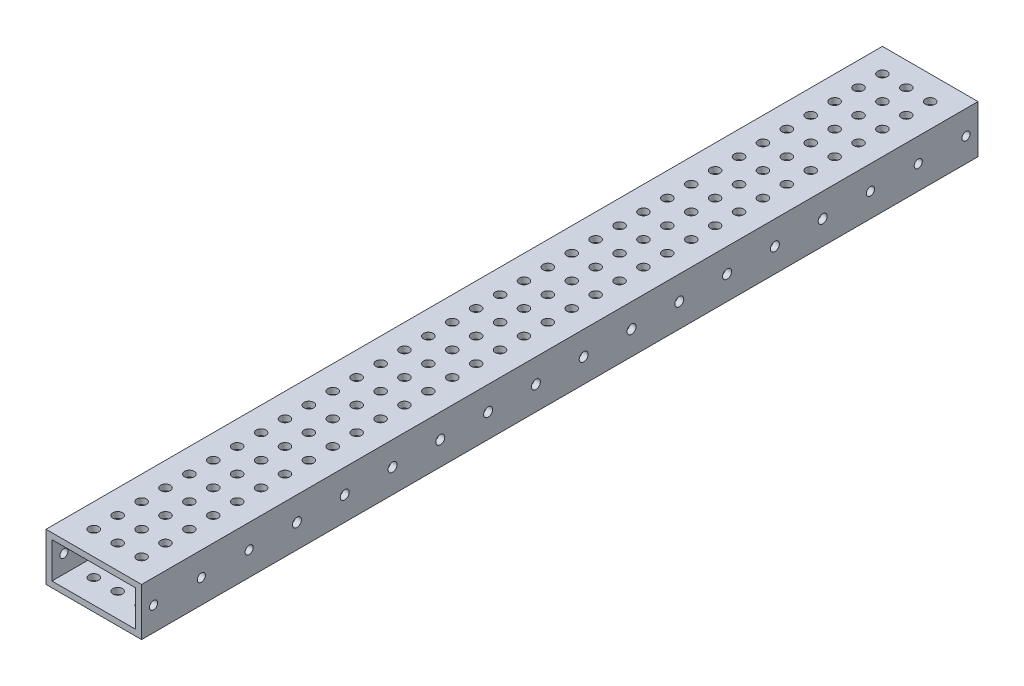
SolidWorks part; units mm, degrees
ref_plane "Front Plane" through (0, 0, 0) normal (0, 0, 1) x (1, 0, 0)
ref_plane "Top Plane" through (0, 0, 0) normal (0, 1, 0) x (1, 0, 0)
ref_plane "Right Plane" through (0, 0, 0) normal (1, 0, 0) x (0, 0, -1)
sketch "Sketch1" plane through (0, 0, 0) normal (0, 0, 1) x (1, 0, 0)
  line L0 (-22.225, 9.525) -> (22.225, 9.525)
  line L1 (-25.4, 12.7) -> (25.4, 12.7)
  line L2 (-25.4, 12.7) -> (-25.4, -12.7)
  line L3 (-25.4, -12.7) -> (25.4, -12.7)
  line L4 (25.4, 12.7) -> (25.4, -12.7)
  line L5 (22.225, 9.525) -> (22.225, -9.525)
  line L6 (-22.225, -9.525) -> (22.225, -9.525)
  line L7 (-22.225, 9.525) -> (-22.225, -9.525)
  line L8 (-25.4, 12.7) -> (25.4, -12.7) construction
  line L9 (25.4, 12.7) -> (-25.4, -12.7) construction
  point P5 (0, 0)
  dimension "D1" = 50.8
  dimension "D2" = 25.4
  dimension "D3" = 3.175
extrude "Boss-Extrude1" add sketch "Sketch1" along normal mid plane 444.5
sketch "Sketch2" plane through (0, 12.7, 0) normal (0, 1, 0) x (1, 0, 0)
  line L0 (25.4, -222.25) -> (-25.4, -222.25) construction
  line L1 (-25.4, -222.25) -> (-25.4, 222.25) construction
  line L2 (-12.7, -209.55) -> (0, -209.55) construction
  line L3 (0, -209.55) -> (12.7, -209.55) construction
  line L4 (25.4, 222.25) -> (-25.4, 222.25) construction
  circle A0 centre (0, -209.55) radius 2.5527
  circle A1 centre (12.7, -209.55) radius 2.5527
  circle A2 centre (-12.7, -209.55) radius 2.5527
  circle A3 centre (-12.7, -196.85) radius 2.5527
  circle A4 centre (0, -196.85) radius 2.5527
  circle A5 centre (12.7, -196.85) radius 2.5527
  circle A6 centre (-12.7, -184.15) radius 2.5527
  circle A7 centre (0, -184.15) radius 2.5527
  circle A8 centre (12.7, -184.15) radius 2.5527
  circle A9 centre (-12.7, -171.45) radius 2.5527
  circle A10 centre (0, -171.45) radius 2.5527
  circle A11 centre (12.7, -171.45) radius 2.5527
  circle A12 centre (-12.7, -158.75) radius 2.5527
  circle A13 centre (0, -158.75) radius 2.5527
  circle A14 centre (12.7, -158.75) radius 2.5527
  circle A15 centre (-12.7, -146.05) radius 2.5527
  circle A16 centre (0, -146.05) radius 2.5527
  circle A17 centre (12.7, -146.05) radius 2.5527
  circle A18 centre (-12.7, -133.35) radius 2.5527
  circle A19 centre (0, -133.35) radius 2.5527
  circle A20 centre (12.7, -133.35) radius 2.5527
  circle A21 centre (-12.7, -120.65) radius 2.5527
  circle A22 centre (0, -120.65) radius 2.5527
  circle A23 centre (12.7, -120.65) radius 2.5527
  circle A24 centre (-12.7, -107.95) radius 2.5527
  circle A25 centre (0, -107.95) radius 2.5527
  circle A26 centre (12.7, -107.95) radius 2.5527
  circle A27 centre (-12.7, -95.25) radius 2.5527
  circle A28 centre (0, -95.25) radius 2.5527
  circle A29 centre (12.7, -95.25) radius 2.5527
  circle A30 centre (-12.7, -82.55) radius 2.5527
  circle A31 centre (0, -82.55) radius 2.5527
  circle A32 centre (12.7, -82.55) radius 2.5527
  circle A33 centre (-12.7, -69.85) radius 2.5527
  circle A34 centre (0, -69.85) radius 2.5527
  circle A35 centre (12.7, -69.85) radius 2.5527
  circle A36 centre (-12.7, -57.15) radius 2.5527
  circle A37 centre (0, -57.15) radius 2.5527
  circle A38 centre (12.7, -57.15) radius 2.5527
  circle A39 centre (-12.7, -44.45) radius 2.5527
  circle A40 centre (0, -44.45) radius 2.5527
  circle A41 centre (12.7, -44.45) radius 2.5527
  circle A42 centre (-12.7, -31.75) radius 2.5527
  circle A43 centre (0, -31.75) radius 2.5527
  circle A44 centre (12.7, -31.75) radius 2.5527
  circle A45 centre (-12.7, -19.05) radius 2.5527
  circle A46 centre (0, -19.05) radius 2.5527
  circle A47 centre (12.7, -19.05) radius 2.5527
  circle A48 centre (-12.7, -6.35) radius 2.5527
  circle A49 centre (0, -6.35) radius 2.5527
  circle A50 centre (12.7, -6.35) radius 2.5527
  circle A51 centre (-12.7, 6.35) radius 2.5527
  circle A52 centre (0, 6.35) radius 2.5527
  circle A53 centre (12.7, 6.35) radius 2.5527
  circle A54 centre (-12.7, 19.05) radius 2.5527
  circle A55 centre (0, 19.05) radius 2.5527
  circle A56 centre (12.7, 19.05) radius 2.5527
  circle A57 centre (-12.7, 31.75) radius 2.5527
  circle A58 centre (0, 31.75) radius 2.5527
  circle A59 centre (12.7, 31.75) radius 2.5527
  circle A60 centre (-12.7, 44.45) radius 2.5527
  circle A61 centre (0, 44.45) radius 2.5527
  circle A62 centre (12.7, 44.45) radius 2.5527
  circle A63 centre (-12.7, 57.15) radius 2.5527
  circle A64 centre (0, 57.15) radius 2.5527
  circle A65 centre (12.7, 57.15) radius 2.5527
  circle A66 centre (-12.7, 69.85) radius 2.5527
  circle A67 centre (0, 69.85) radius 2.5527
  circle A68 centre (12.7, 69.85) radius 2.5527
  circle A69 centre (-12.7, 82.55) radius 2.5527
  circle A70 centre (0, 82.55) radius 2.5527
  circle A71 centre (12.7, 82.55) radius 2.5527
  circle A72 centre (-12.7, 95.25) radius 2.5527
  circle A73 centre (0, 95.25) radius 2.5527
  circle A74 centre (12.7, 95.25) radius 2.5527
  circle A75 centre (-12.7, 107.95) radius 2.5527
  circle A76 centre (0, 107.95) radius 2.5527
  circle A77 centre (12.7, 107.95) radius 2.5527
  circle A78 centre (-12.7, 120.65) radius 2.5527
  circle A79 centre (0, 120.65) radius 2.5527
  circle A80 centre (12.7, 120.65) radius 2.5527
  circle A81 centre (-12.7, 133.35) radius 2.5527
  circle A82 centre (0, 133.35) radius 2.5527
  circle A83 centre (12.7, 133.35) radius 2.5527
  circle A84 centre (-12.7, 146.05) radius 2.5527
  circle A85 centre (0, 146.05) radius 2.5527
  circle A86 centre (12.7, 146.05) radius 2.5527
  circle A87 centre (-12.7, 158.75) radius 2.5527
  circle A88 centre (0, 158.75) radius 2.5527
  circle A89 centre (12.7, 158.75) radius 2.5527
  circle A90 centre (-12.7, 171.45) radius 2.5527
  circle A91 centre (0, 171.45) radius 2.5527
  circle A92 centre (12.7, 171.45) radius 2.5527
  circle A93 centre (-12.7, 184.15) radius 2.5527
  circle A94 centre (0, 184.15) radius 2.5527
  circle A95 centre (12.7, 184.15) radius 2.5527
  circle A96 centre (-12.7, 196.85) radius 2.5527
  circle A97 centre (0, 196.85) radius 2.5527
  circle A98 centre (12.7, 196.85) radius 2.5527
  circle A99 centre (-12.7, 209.55) radius 2.5527
  circle A100 centre (0, 209.55) radius 2.5527
  circle A101 centre (12.7, 209.55) radius 2.5527
  circle A108 centre (-12.7, 234.95) radius 2.5527 [skipped]
  circle A109 centre (0, 234.95) radius 2.5527 [skipped]
  circle A110 centre (12.7, 234.95) radius 2.5527 [skipped]
  circle A111 centre (-12.7, 222.25) radius 2.5527 [skipped]
  circle A112 centre (0, 222.25) radius 2.5527 [skipped]
  circle A113 centre (12.7, 222.25) radius 2.5527 [skipped]
  dimension "D2" = 5.1054
  dimension "D4" = 12.7
  dimension "D1" = 12.7
  dimension "D3" = 25.4
  dimension "D6" = 12.7
  dimension "D7" = 12.7
  dimension "D5" = 36
extrude "Cut-Extrude1" cut sketch "Sketch2" against normal through all
sketch "Sketch3" plane through (25.4, 0, 0) normal (1, 0, 0) x (0, 0, -1)
  line L0 (-222.25, -12.7) -> (-222.25, 12.7) construction
  line L1 (-222.25, 12.7) -> (222.25, 12.7) construction
  line L2 (222.25, -12.7) -> (222.25, 12.7) construction
  circle A0 centre (-215.9, 0) radius 2.159
  circle A1 centre (-190.5, 0) radius 2.159
  circle A2 centre (-165.1, 0) radius 2.159
  circle A3 centre (215.9, 0) radius 2.159
  circle A4 centre (190.5, 0) radius 2.159
  circle A5 centre (165.1, 0) radius 2.159
  dimension "D2" = 4.318
  dimension "D9" = 4.318
  dimension "D1" = 6.35
  dimension "D3" = 12.7
  dimension "D4" = 31.75
  dimension "D5" = 12.7
  dimension "D6" = 57.15
  dimension "D7" = 12.7
  dimension "D8" = 6.35
  dimension "D10" = 12.7
  dimension "D11" = 31.75
  dimension "D12" = 57.15
  dimension "D13" = 12.7
  dimension "D14" = 12.7
extrude "Cut-Extrude2" cut sketch "Sketch3" against normal through all
sketch "Sketch4" plane through (25.4, 0, 0) normal (1, 0, 0) x (0, 0, -1)
  line L0 (-222.25, -12.7) -> (-222.25, 12.7) construction
  line L1 (-222.25, 0) -> (-215.9, 0) construction
  circle A1 centre (-215.9, 0) radius 2.3813 construction
  circle A2 centre (-190.5, 0) radius 2.3813 construction
  circle A3 centre (-165.1, 0) radius 2.3813 construction
  circle A4 centre (-139.7, 0) radius 2.3813
  circle A5 centre (-114.3, 0) radius 2.3813
  circle A6 centre (-88.9, 0) radius 2.3813
  circle A7 centre (-63.5, 0) radius 2.3813
  circle A8 centre (-38.1, 0) radius 2.3813
  circle A9 centre (-12.7, 0) radius 2.3813
  circle A10 centre (12.7, 0) radius 2.3813
  circle A11 centre (38.1, 0) radius 2.3813
  circle A12 centre (63.5, 0) radius 2.3813
  circle A13 centre (88.9, 0) radius 2.3813
  circle A14 centre (114.3, 0) radius 2.3813
  circle A15 centre (139.7, 0) radius 2.3813
  circle A16 centre (165.1, 0) radius 2.3813 construction
  circle A17 centre (190.5, 0) radius 2.3813 construction
  circle A18 centre (215.9, 0) radius 2.3813 construction
  dimension "D2" = 18
  dimension "D1" = 4.7625
  dimension "D3" = 25.4
  dimension "D4" = 6.35
extrude "Cut-Extrude3" cut sketch "Sketch4" against normal through all
other "Freeze***"
